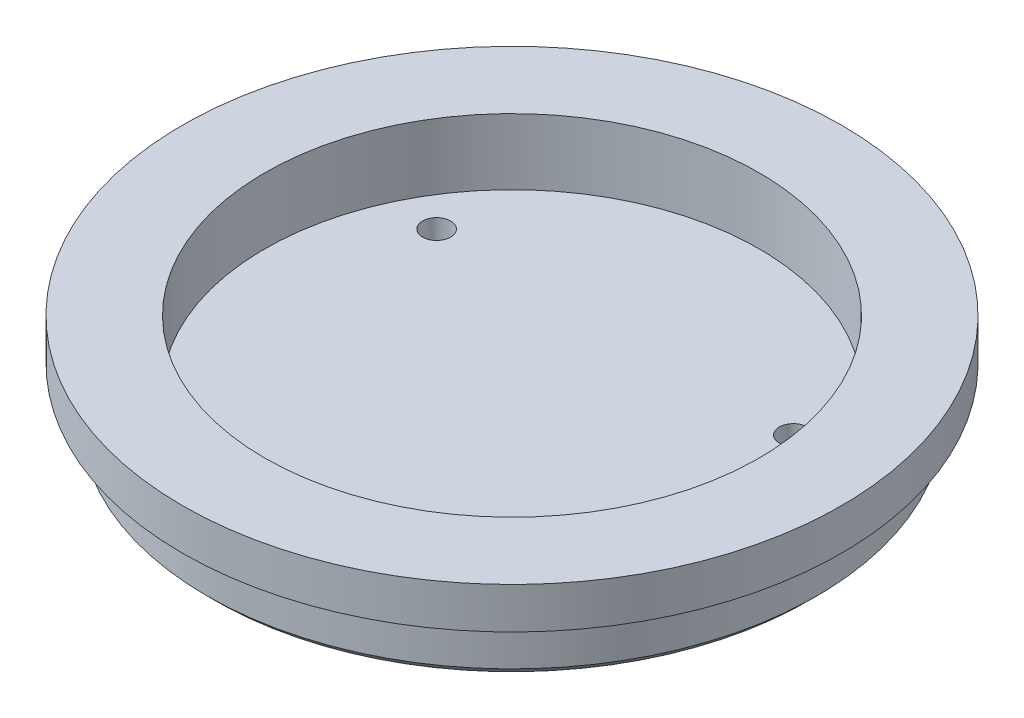
SolidWorks part; units mm, degrees
material "1060 合金"
ref_plane "前视基准面" through (0, 0, 0) normal (0, 0, 1) x (1, 0, 0)
ref_plane "上视基准面" through (0, 0, 0) normal (0, 1, 0) x (1, 0, 0)
ref_plane "右视基准面" through (0, 0, 0) normal (1, 0, 0) x (0, 0, -1)
sketch "草图1" plane through (0, 0, 0) normal (1, 0, 0) x (0, 0, -1)
  line L0 (0, 0) -> (0, 53.2892) construction
  line L1 (0, 0) -> (37, 0)
  line L2 (37, 0) -> (37, 7)
  line L3 (37, 7) -> (40, 7)
  line L4 (40, 7) -> (40, 12)
  line L5 (40, 12) -> (0, 12)
  line L6 (0, 0) -> (0, 12)
  dimension "D1" = 37
  dimension "D2" = 7
  dimension "D3" = 5
  dimension "D4" = 40
revolve "旋转1" add sketch "草图1" angle 360 about L0
chamfer "倒角1" distance 1 angle 45 1 edges at (0, 0, -37)
hole_wizard "M3 间隙孔1" positions "草图3" profile "草图2" hole size "M3" standard "GB" end condition through all
sketch "草图3" plane through (0, 12, 0) normal (0, -1, 0) x (-1, 0, 0)
  circle A0 centre (0, 0) radius 25 construction
  point P5 (0, -25)
  point P28 (-21.6506, 12.5)
  point P29 (21.6506, 12.5)
  dimension "D1" = 50
  dimension "D2" = 3
sketch "草图2" plane through (0, 12, 25) normal (1, 0, 0) x (0, 0, 1)
  line L0 (0, 0) -> (0, 12)
  line L1 (0, 12) -> (1.7, 12)
  line L2 (1.7, 12) -> (1.7, 0)
  line L5 (1.7, 0) -> (0, 0)
  line L11 (0, -6.35) -> (0, 107.95) construction
  dimension "通孔孔直径" = 3.4
  dimension "通孔孔深度" = 12
sketch "草图4" plane through (0, 12, 0) normal (0, 1, 0) x (1, 0, 0)
  circle A0 centre (0, 0) radius 30
  dimension "D1" = 60
extrude "切除-拉伸1" cut sketch "草图4" against normal blind 8
